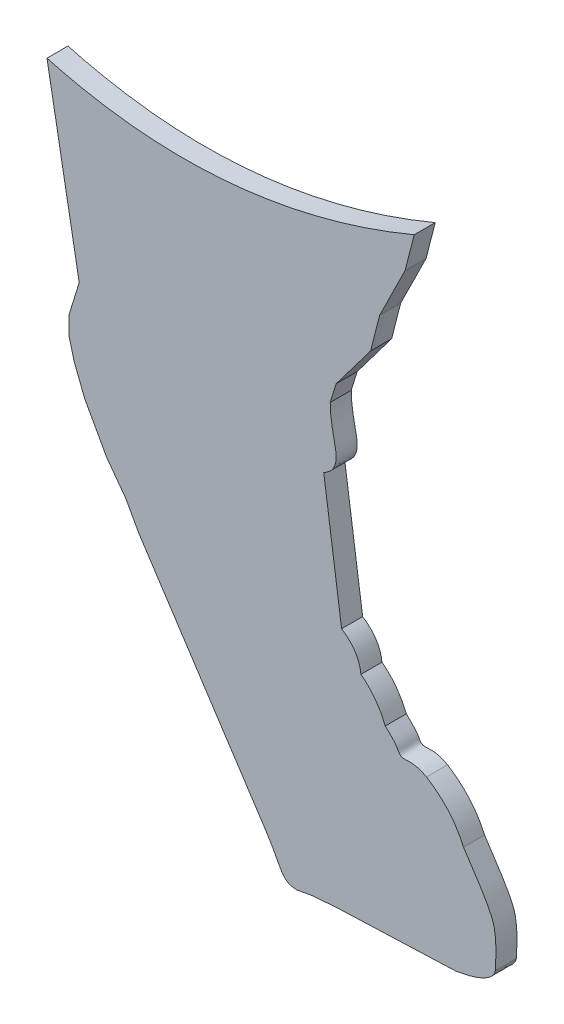
SolidWorks part; units mm, degrees
ref_plane "Front Plane" through (0, 0, 0) normal (0, 0, 1) x (1, 0, 0)
ref_plane "Top Plane" through (0, 0, 0) normal (0, 1, 0) x (1, 0, 0)
ref_plane "Right Plane" through (0, 0, 0) normal (1, 0, 0) x (0, 0, -1)
sketch "Sketch1" plane through (0, 0, 0) normal (0, 0, 1) x (1, 0, 0)
  line L0 (134.6667, 500.5) -> (673.3333, 500.5) construction
  line L1 (95.0151, 73.0396) -> (93.4424, 67.9472)
  line L2 (93.4424, 67.9472) -> (93.4424, 65.401)
  line L3 (93.4424, 65.401) -> (94.2288, 62.4055)
  line L4 (94.2288, 62.4055) -> (95.8389, 58.2866)
  line L5 (95.8389, 58.2866) -> (97.8609, 54.617)
  line L6 (97.8609, 54.617) -> (99.1877, 52.209)
  line L7 (99.1877, 52.209) -> (102.0546, 48.3264)
  line L8 (102.0546, 48.3264) -> (104.0449, 44.7143)
  line L9 (104.0449, 44.7143) -> (123.0328, 15.7186)
  line L10 (127.9651, 10.0937) -> (130.0459, 10.4701)
  line L11 (130.0459, 10.4701) -> (133.7876, 10.7747)
  line L12 (133.7876, 10.7747) -> (151.9742, 11.4708)
  line L14 (133.7876, 79.1971) -> (132.8975, 76.3148)
  line L15 (131.9168, 66.6741) -> (134.5134, 48.3264)
  line L16 (134.5134, 48.3264) -> (134.6174, 47.5914)
  line L18 (133.7876, 79.1971) -> (138.9956, 86.1016)
  line L19 (138.9956, 86.1016) -> (140.3613, 91.4507)
  line L20 (140.3613, 91.4507) -> (143.1224, 97.0274)
  line L21 (143.1224, 97.0274) -> (144.2001, 99.204)
  line L22 (144.2001, 99.204) -> (145.5707, 104.5722)
  line L23 (95.0151, 73.0396) -> (92.4998, 86.9439)
  line L24 (92.4998, 86.9439) -> (90.1483, 99.9431)
  spline S0 degree 3 poles (123.0328, 15.7186) (123.7143, 14.7232) (125.0279, 12.417) (126.1313, 9.9933) (127.9651, 10.0937) knots 0 0 0 0 0.482545 1 1 1 1
  spline S1 degree 3 poles (141.2086, 38.1802) (142.0578, 37.3364) (142.6965, 36.8317) (143.8648, 34.5581) (144.8079, 36.0573) (147.4373, 34.6374) knots 0 0 0 0 0.387994 0.411005 1 1 1 1
  spline S2 degree 2 poles (147.4373, 34.6374) (151.3117, 32.1818) (153.0172, 28.2463) knots 0 0 0 1 1 1
  spline S3 degree 3 poles (153.0172, 28.2463) (155.0535, 25.0973) (156.1686, 23.6544) (158.1463, 19.3121) (157.9006, 15.9258) (157.8294, 14.5022) knots 0 0 0 0 0.545638 0.593854 1 1 1 1
  spline S4 degree 3 poles (157.8294, 14.5022) (157.371, 12.4487) (153.4132, 11.7402) (151.9742, 11.4708) knots 0 0 0 0 1 1 1 1
  spline S5 degree 2 poles (90.1483, 99.9431) (116.963, 92.5784) (145.5707, 104.5722) knots 0 0 0 1 1 1
  spline S6 degree 3 poles (132.8975, 76.3148) (132.9159, 73.1979) (134.3834, 69.9755) (133.3842, 67.4244) (131.9168, 66.6741) knots 0 0 0 0 0.575324 1 1 1 1
  spline S7 degree 2 poles (134.6174, 47.5914) (137.2297, 45.9166) (137.5361, 43.0923) knots 0 0 0 1 1 1
  spline S8 degree 2 poles (137.5361, 43.0923) (139.9841, 41.2453) (141.2086, 38.1802) knots 0 0 0 1 1 1
extrude "Boss-Extrude2" add sketch "Sketch1" along normal blind 3.175
